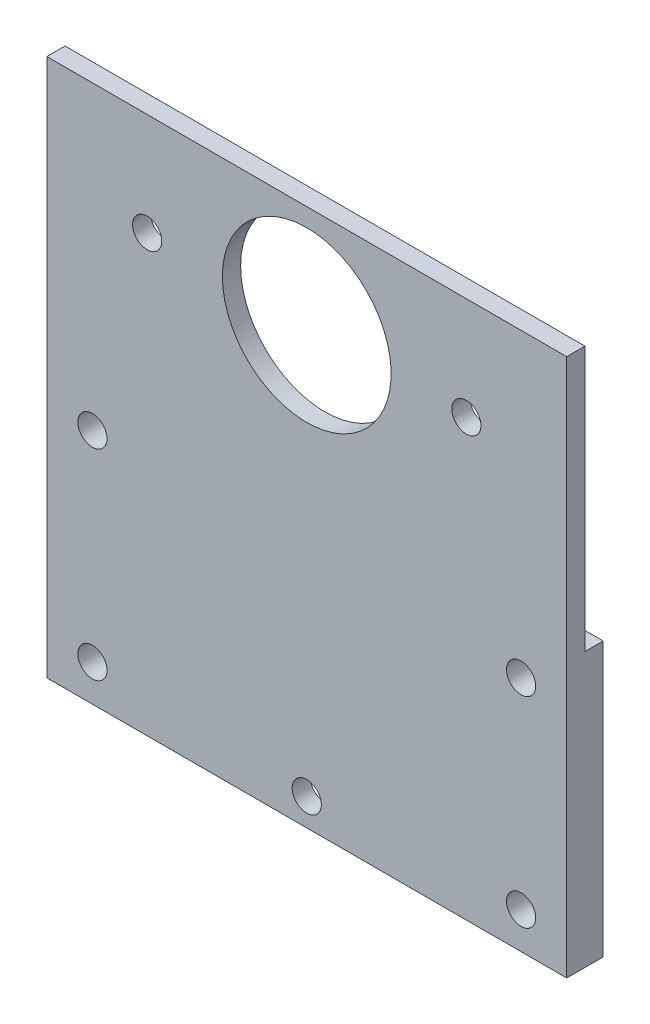
SolidWorks part; units mm, degrees
ref_plane "Ebene vorne" through (0, 0, 0) normal (0, 0, 1) x (1, 0, 0)
ref_plane "Ebene oben" through (0, 0, 0) normal (0, 1, 0) x (1, 0, 0)
ref_plane "Ebene rechts" through (0, 0, 0) normal (1, 0, 0) x (0, 0, -1)
sketch "Skizze1" plane through (0, 0, 0) normal (0, 0, 1) x (1, 0, 0)
  line L0 (0, 0) -> (0, 72.9146) construction
  line L1 (-28.5, 59) -> (28.5, 59)
  line L2 (28.5, 59) -> (28.5, 0)
  line L3 (28.5, 0) -> (-28.5, 0)
  line L4 (-28.5, 59) -> (-28.5, 0)
  point P7 (0, 59)
  dimension "D1" = 57
  dimension "D2" = 59
extrude "Grundkörper" add sketch "Skizze1" along normal blind 2
sketch "Skizze2" plane through (0, 0, 0) normal (0, 0, -1) x (-1, 0, 0)
  line L0 (0, 0) -> (0, 59.4137) construction
  line L1 (-18.082, 47.75) -> (18.082, 47.75) construction
  line L2 (-28.5, 59) -> (28.5, 59) construction
  circle A0 centre (0, 47.75) radius 9.25
  circle A1 centre (-17.5, 47.75) radius 1.6
  circle A2 centre (17.5, 47.75) radius 1.6
  dimension "D1" = 3.2
  dimension "D2" = 18.5
  dimension "D3" = 11.25
  dimension "D4" = 35
extrude "Bohrungen_Kugelroller" cut sketch "Skizze2" against normal through all
sketch "Skizze3" plane through (0, 0, 0) normal (0, 0, -1) x (-1, 0, 0)
  line L0 (0, 59) -> (0, -0.4438) construction
  line L1 (-28.5, 59) -> (28.5, 59) construction
  line L2 (-28.5, 30) -> (-18.5, 30)
  line L3 (-28.5, 0) -> (-28.5, 59) construction
  line L4 (-18.5, 30) -> (-18.5, 0)
  line L5 (28.5, 0) -> (18.5, 0)
  line L6 (28.5, 30) -> (28.5, 0)
  line L7 (-28.5, 30) -> (-28.5, 0)
  line L8 (-28.5, 0) -> (-18.5, 0)
  line L9 (28.5, 0) -> (-28.5, 0) construction
  line L10 (18.5, 30) -> (18.5, 0)
  line L11 (28.5, 30) -> (18.5, 30)
  dimension "D1" = 10
  dimension "D2" = 30
extrude "Aufsatz_Getriebehalter" add sketch "Skizze3" along normal blind 2
sketch "Skizze4" plane through (0, 0, -2) normal (0, 0, -1) x (-1, 0, 0)
  line L0 (0, 57.8388) -> (0, -14.2703) construction
  line L1 (24, 15) -> (-24, 15) construction
  line L2 (-23.5, 30) -> (-23.5, -0.0042) construction
  line L3 (24, 22.0317) -> (24, 7.9683) construction
  line L4 (-18.5, 15) -> (-29.1223, 15) construction
  line L5 (-18.5, 0) -> (-18.5, 30) construction
  line L7 (-18.5, 30) -> (-28.5, 30) construction
  circle A0 centre (-23.5, 26) radius 1.6
  circle A1 centre (23.5, 26) radius 1.6
  circle A2 centre (23.5, 4) radius 1.6
  circle A3 centre (-23.5, 4) radius 1.6
  point P10 (0, 15)
  dimension "D1" = 3.2
  dimension "D2" = 22
extrude "Bohrungen_Getriebehalter" cut sketch "Skizze4" against normal through all
sketch "Skizze5" plane through (0, 0, 0) normal (0, 0, -1) x (-1, 0, 0)
  line L0 (0, 61.2734) -> (0, -5.0948) construction
  line L1 (18.5, 0) -> (-18.5, 0) construction
  circle A0 centre (0, 3) radius 1.6
  dimension "D1" = 3.2
  dimension "D2" = 3
extrude "Bohrung_Halterung" cut sketch "Skizze5" against normal through all
sketch "Skizze8" plane through (0, 0, 0) normal (0, 0, -1) x (-1, 0, 0)
  line L0 (-16.5, 13) -> (-16.5, 3)
  line L1 (-16.5, 3) -> (-4, 3)
  line L2 (-4, 3) -> (-4, 7.5)
  line L3 (-4, 7.5) -> (-16.5, 13)
  line L4 (-4, 9.5) -> (-4, 20.5)
  line L5 (-4, 20.5) -> (-16.5, 15)
  line L6 (-16.5, 15) -> (-4, 9.5)
  line L7 (-16.5, 28) -> (-16.5, 17)
  line L8 (-16.5, 17) -> (-4, 22.5)
  line L9 (-4, 22.5) -> (-16.5, 28)
  line L10 (-16.5, 30) -> (-4, 24.5)
  line L11 (-4, 24.5) -> (-4, 35.5)
  line L12 (-4, 35.5) -> (-16.5, 30)
  line L13 (0, 0) -> (0, 65.3922) construction
  line L14 (-26.178, 32) -> (-16.5, 32)
  line L15 (-16.5, 32) -> (-4, 37.5)
  line L16 (-18.5, 0) -> (-18.5, 30) construction
  line L17 (18.5, 0) -> (-18.5, 0) construction
  line L18 (-4, 37.5) -> (-26.178, 37.5)
  line L19 (-26.178, 37.5) -> (-26.178, 32)
  line L20 (-18.5, 30) -> (-28.5, 30) construction
  line L21 (26.178, 37.5) -> (26.178, 32)
  line L22 (4, 37.5) -> (26.178, 37.5)
  line L23 (16.5, 32) -> (4, 37.5)
  line L24 (26.178, 32) -> (16.5, 32)
  line L25 (4, 35.5) -> (16.5, 30)
  line L26 (4, 24.5) -> (4, 35.5)
  line L27 (16.5, 30) -> (4, 24.5)
  line L28 (4, 22.5) -> (16.5, 28)
  line L29 (16.5, 17) -> (4, 22.5)
  line L30 (16.5, 28) -> (16.5, 17)
  line L31 (16.5, 15) -> (4, 9.5)
  line L32 (4, 20.5) -> (16.5, 15)
  line L33 (4, 9.5) -> (4, 20.5)
  line L34 (4, 7.5) -> (16.5, 13)
  line L35 (4, 3) -> (4, 7.5)
  line L36 (16.5, 3) -> (4, 3)
  line L37 (16.5, 13) -> (16.5, 3)
  dimension "D1" = 2
  dimension "D2" = 4
  dimension "D3" = 3
  dimension "D4" = 10
  dimension "D5" = 2
  dimension "D6" = 2
  dimension "D7" = 2
  dimension "D8" = 11
  dimension "D9" = 2
extrude "Schnitt-Linear austragen4" cut sketch "Skizze8" against normal blind 1
fillet "Verrundung_Ausschnitte" radius 1 34 edges at (-26.178, 34.75, 1) (-21.339, 32, 1) (-10.25, 34.75, 1) (-15.089, 37.5, 1) (-10.25, 32.75, 1) (-10.25, 27.25, 1) (-4, 30, 1) (-10.25, 25.25, 1) (-16.5, 22.5, 1) (-10.25, 19.75, 1) (-10.25, 12.25, 1) (-4, 15, 1) (-10.25, 17.75, 1) (-10.25, 10.25, 1) (-16.5, 8, 1) (-10.25, 3, 1) (-4, 5.25, 1) (4, 5.25, 1) (10.25, 3, 1) (16.5, 8, 1) (10.25, 10.25, 1) (10.25, 17.75, 1) (4, 15, 1) (10.25, 12.25, 1) (10.25, 19.75, 1) (16.5, 22.5, 1) (10.25, 25.25, 1) (4, 30, 1) (10.25, 27.25, 1) (10.25, 32.75, 1) (10.25, 34.75, 1) (21.339, 32, 1) (26.178, 34.75, 1) (15.089, 37.5, 1)
fillet "Verrundung4" radius 1 34 edges at (5.3929, 37.2071, 0.7071) (4.2929, 3.2929, 0.7071) (16.2071, 3.2929, 0.7071) (4.2929, 9.9489, 0.7071) (15.7727, 15, 0.7071) (4.2929, 7.3089, 0.7071) (16.2071, 12.5511, 0.7071) (4.2929, 20.0511, 0.7071) (4.7273, 22.5, 0.7071) (16.2071, 17.4489, 0.7071) (16.2071, 27.5511, 0.7071) (4.2929, 35.0511, 0.7071) (4.2929, 24.9489, 0.7071) (15.7727, 30, 0.7071) (16.5616, 32.2929, 0.7071) (25.8851, 32.2929, 0.7071) (25.8851, 37.2071, 0.7071) (-16.2071, 3.2929, 0.7071) (-16.2071, 12.5511, 0.7071) (-4.2929, 3.2929, 0.7071) (-4.2929, 7.3089, 0.7071) (-4.2929, 20.0511, 0.7071) (-4.2929, 9.9489, 0.7071) (-15.7727, 15, 0.7071) (-16.2071, 17.4489, 0.7071) (-16.2071, 27.5511, 0.7071) (-4.7273, 22.5, 0.7071) (-15.7727, 30, 0.7071) (-4.2929, 35.0511, 0.7071) (-4.2929, 24.9489, 0.7071) (-5.3929, 37.2071, 0.7071) (-16.5616, 32.2929, 0.7071) (-25.8851, 37.2071, 0.7071) (-25.8851, 32.2929, 0.7071)
